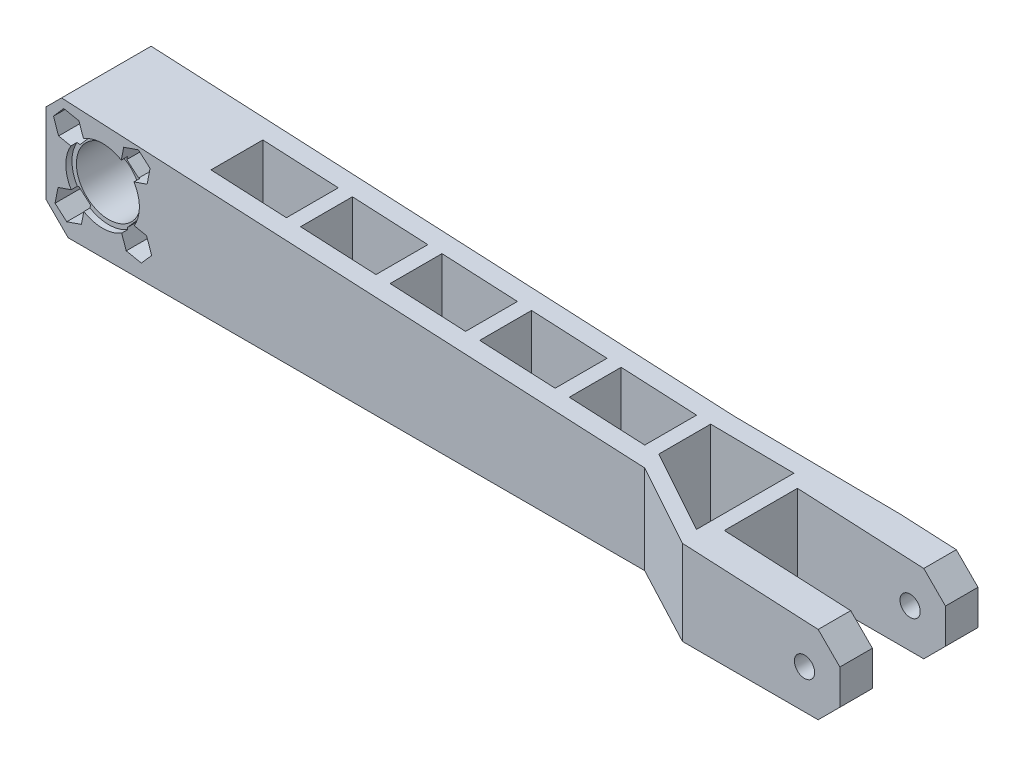
SolidWorks part; units mm, degrees
ref_plane "前视基准面" through (0, 0, 0) normal (0, 0, 1) x (1, 0, 0)
ref_plane "上视基准面" through (0, 0, 0) normal (0, 1, 0) x (1, 0, 0)
ref_plane "右视基准面" through (0, 0, 0) normal (1, 0, 0) x (0, 0, -1)
sketch "草图1" plane through (0, 0, 0) normal (0, 1, 0) x (1, 0, 0)
  line L0 (0, 0) -> (0, 19)
  line L1 (0, 19) -> (127, 19)
  line L2 (127, 19) -> (161, 20.3)
  line L3 (161, 20.3) -> (177.4, 20.3)
  line L7 (177.4, -9) -> (144, -9)
  line L8 (144, -9) -> (127, 0)
  line L9 (127, 0) -> (0, 0)
  line L10 (177.4, -9) -> (177.4, -2.1)
  line L11 (177.4, -2.1) -> (146, -2.1)
  line L13 (146, -2.1) -> (146, 13.4)
  line L15 (146, 13.4) -> (177.4, 13.4)
  line L16 (177.4, 13.4) -> (177.4, 20.3)
  line L17 (0, 9.5) -> (148.8744, 9.5) construction
  line L18 (31, 15) -> (47, 15)
  line L19 (31, 15) -> (31, 4)
  line L20 (31, 4) -> (47, 4)
  line L21 (47, 15) -> (47, 4)
  line L22 (126, 15) -> (126, 4)
  line L23 (50, 4) -> (66, 4)
  line L24 (50, 4) -> (50, 15)
  line L25 (50, 15) -> (66, 15)
  line L26 (66, 4) -> (66, 15)
  line L27 (69, 4) -> (85, 4)
  line L28 (69, 4) -> (69, 15)
  line L29 (69, 15) -> (85, 15)
  line L30 (85, 4) -> (85, 15)
  line L31 (126, 4) -> (143, -5)
  line L32 (143, -5) -> (143, 15.65)
  line L33 (143, 15.65) -> (126, 15)
  line L34 (88, 4) -> (88, 15)
  line L35 (88, 4) -> (104, 4)
  line L36 (104, 4) -> (104, 15)
  line L37 (88, 15) -> (104, 15)
  line L38 (107, 4) -> (107, 15)
  line L39 (107, 4) -> (123, 4)
  line L40 (123, 4) -> (123, 15)
  line L41 (107, 15) -> (123, 15)
  dimension "D1" = 15.5
  dimension "D2" = 19
  dimension "D3" = 6.9
  dimension "D4" = 6.9
  dimension "D5" = 31.4
  dimension "D6" = 33.4
  dimension "D7" = 9
  dimension "D8" = 16.4
  dimension "D9" = 20
  dimension "D10" = 126
  dimension "D11" = 1
  dimension "D12" = 31
  dimension "D13" = 11
  dimension "D14" = 16
  dimension "D15" = 3
  dimension "D16" = 3
  dimension "D17" = 16
  dimension "D18" = 16
  dimension "D19" = 3
  dimension "D20" = 3
extrude "凸台-拉伸1" add sketch "草图1" along normal blind 25
sketch "草图2" plane through (0, 0, 9) normal (0, 0, 1) x (1, 0, 0)
  line L0 (0, 21.7012) -> (3.2988, 25)
  line L1 (0, 25) -> (0, 0) construction
  line L2 (0, 25) -> (127, 25) construction
  line L3 (3.2988, 25) -> (172.7967, 16.6065)
  line L5 (172.7967, 16.6065) -> (177.4, 12.0033)
  line L6 (177.4, 25) -> (177.4, 0) construction
  line L7 (177.4, 12.0033) -> (177.4, 4.6033)
  line L8 (177.4, 4.6033) -> (172.7967, 0)
  line L9 (144, 0) -> (177.4, 0) construction
  line L10 (172.7967, 0) -> (4.7012, 0)
  line L11 (0, 0) -> (127, 0) construction
  line L12 (4.7012, 0) -> (0, 4.7012)
  line L13 (0, 4.7012) -> (0, 21.7012)
  line L14 (0, 13.2012) -> (18.5484, 13.2012) construction
  line L15 (177.4, 8.3033) -> (161.5581, 8.3033) construction
  circle A0 centre (169.9, 8.3033) radius 2.15
  circle A1 centre (12, 13.2012) radius 6.85
  dimension "D7" = 45
  dimension "D8" = 12
  dimension "D9" = 7.5
  dimension "D6" = 157.9
  dimension "D13" = 13.7
  dimension "D14" = 4.3
  dimension "D2" = 17
  dimension "D3" = 45
  dimension "D4" = 45
  dimension "D5" = 7.4
  dimension "D10" = 6.51
  dimension "D11" = 6.51
  dimension "D12" = 45
extrude "切除-拉伸1" cut sketch "草图2" against normal through all flip side to cut
sketch "草图3" plane through (0, 0, 0) normal (0, 0, 1) x (1, 0, 0)
  circle A0 centre (12, 13.2012) radius 7.8
  dimension "D1" = 15.6
extrude "切除-拉伸2" cut sketch "草图3" against normal blind 1.3
sketch "草图4" plane through (0, 0, -19) normal (0, 0, -1) x (-1, 0, 0)
  circle A0 centre (-12, 13.2012) radius 7.85
  dimension "D1" = 15.7
extrude "切除-拉伸3" cut sketch "草图4" against normal blind 1.3
sketch "草图5" plane through (0, 0, 0) normal (0, 0, 1) x (1, 0, 0)
  line L0 (15.8552, 19.3047) -> (18.3377, 17.1444)
  line L1 (5.8965, 17.0564) -> (8.0568, 19.5389)
  line L2 (8.0568, 19.5389) -> (6.987, 22.6511)
  line L3 (6.987, 22.6511) -> (3.7569, 23.2807)
  line L4 (3.7569, 23.2807) -> (1.5966, 20.7981)
  line L5 (1.5966, 20.7981) -> (2.6664, 17.686)
  line L6 (2.6664, 17.686) -> (5.8965, 17.0564)
  line L7 (18.3377, 17.1444) -> (21.4499, 18.2142)
  line L8 (21.4499, 18.2142) -> (22.0795, 21.4444)
  line L9 (22.0795, 21.4444) -> (19.5969, 23.6047)
  line L10 (19.5969, 23.6047) -> (16.4848, 22.5349)
  line L11 (16.4848, 22.5349) -> (15.8552, 19.3047)
  line L12 (18.1035, 9.3461) -> (15.9432, 6.8635)
  line L13 (15.9432, 6.8635) -> (17.013, 3.7514)
  line L14 (17.013, 3.7514) -> (20.2431, 3.1218)
  line L15 (20.2431, 3.1218) -> (22.4034, 5.6043)
  line L16 (22.4034, 5.6043) -> (21.3336, 8.7165)
  line L17 (21.3336, 8.7165) -> (18.1035, 9.3461)
  line L18 (8.1448, 7.0977) -> (5.6623, 9.258)
  line L19 (5.6623, 9.258) -> (2.5501, 8.1882)
  line L20 (2.5501, 8.1882) -> (1.9205, 4.9581)
  line L21 (1.9205, 4.9581) -> (4.4031, 2.7978)
  line L22 (4.4031, 2.7978) -> (7.5152, 3.8676)
  line L23 (7.5152, 3.8676) -> (8.1448, 7.0977)
  circle A5 centre (4.8267, 20.1685) radius 2.85 construction
  circle A6 centre (12, 13.2012) radius 6.85 construction
  circle A7 centre (4.8267, 20.1685) radius 1.5056
  circle A8 centre (18.9673, 20.3745) radius 1.5056
  circle A9 centre (19.1733, 6.2339) radius 1.5056
  circle A10 centre (5.0327, 6.0279) radius 1.5056
  point P31 (12, 13.2012)
  point P39 (12, 13.2012)
  dimension "D1" = 5.7
  dimension "D2" = 10
  dimension "D3" = 4
extrude "切除-拉伸5" cut sketch "草图5" against normal blind 7 contours L18 L19 L20 L21 L22 L23 | L1 L2 L3 L4 L5 L6 | L0 L7 L8 L9 L10 L11 | L12 L13 L14 L15 L16 L17
extrude "切除-拉伸6" cut sketch "草图5<3>" against normal through all contours A10 | A7 | A8 | A9 region at (4.8267, 20.1685, 0) region at (18.9673, 20.3745, 0) region at (19.1733, 6.2339, 0) region at (5.0327, 6.0279, 0)
sketch "草图5<3>" plane through (0, 0, 0) normal (0, 0, 1) x (1, 0, 0) same geometry as "草图5"
